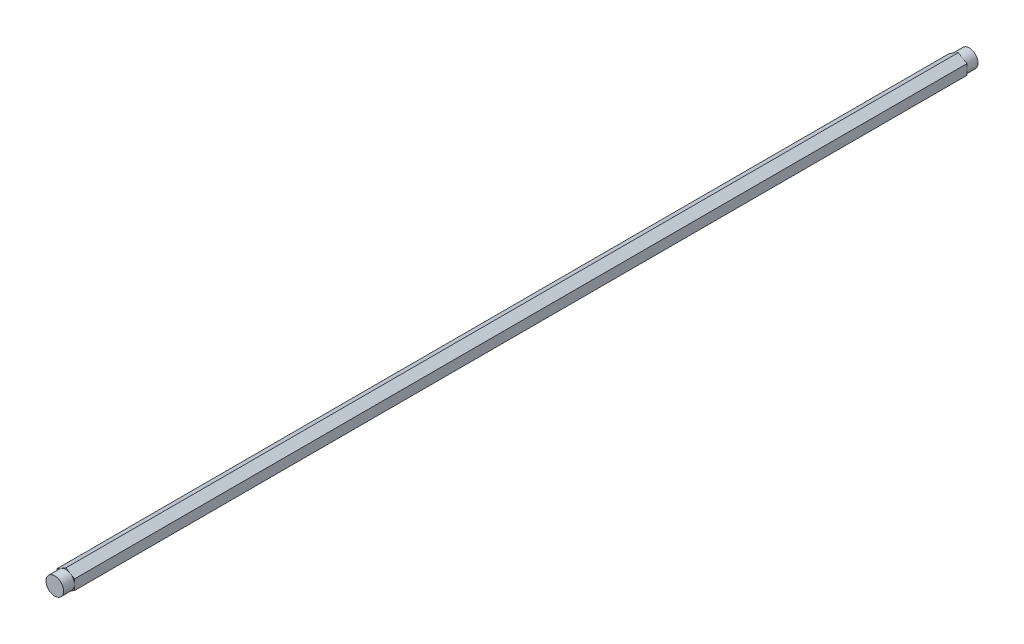
SolidWorks part; units mm, degrees
material "7075-T6 (SN)"
ref_plane "Front Plane" through (0, 0, 0) normal (0, 0, 1) x (1, 0, 0)
ref_plane "Top Plane" through (0, 0, 0) normal (0, 1, 0) x (1, 0, 0)
ref_plane "Right Plane" through (0, 0, 0) normal (1, 0, 0) x (0, 0, -1)
sketch "Sketch1" plane through (0, 0, 0) normal (0, 0, 1) x (1, 0, 0)
  line L1 (0, 7.3323) -> (-6.35, 3.6662)
  line L2 (-6.35, 3.6662) -> (-6.35, -3.6662)
  line L3 (-6.35, -3.6662) -> (0, -7.3323)
  line L4 (0, -7.3323) -> (6.35, -3.6662)
  line L5 (6.35, -3.6662) -> (6.35, 3.6662)
  line L6 (6.35, 3.6662) -> (0, 7.3323)
  circle A0 centre (0, 0) radius 6.35 construction
  dimension "D1" = 12.7
extrude "Boss-Extrude1" add sketch "Sketch1" along normal mid plane 660.4
sketch "Sketch2" plane through (0, 0, -330.2) normal (0, 0, -1) x (-1, 0, 0)
  circle A0 centre (0, 0) radius 6.35
  dimension "D1" = 12.7
extrude "Cut-Extrude-Thin1" cut sketch "Sketch2" against normal blind 7.9375 thin thin type one direction wall 2.54
mirror "Mirror1" about plane through (0, 0, 0) normal (0, 0, 1) of "Cut-Extrude-Thin1"
